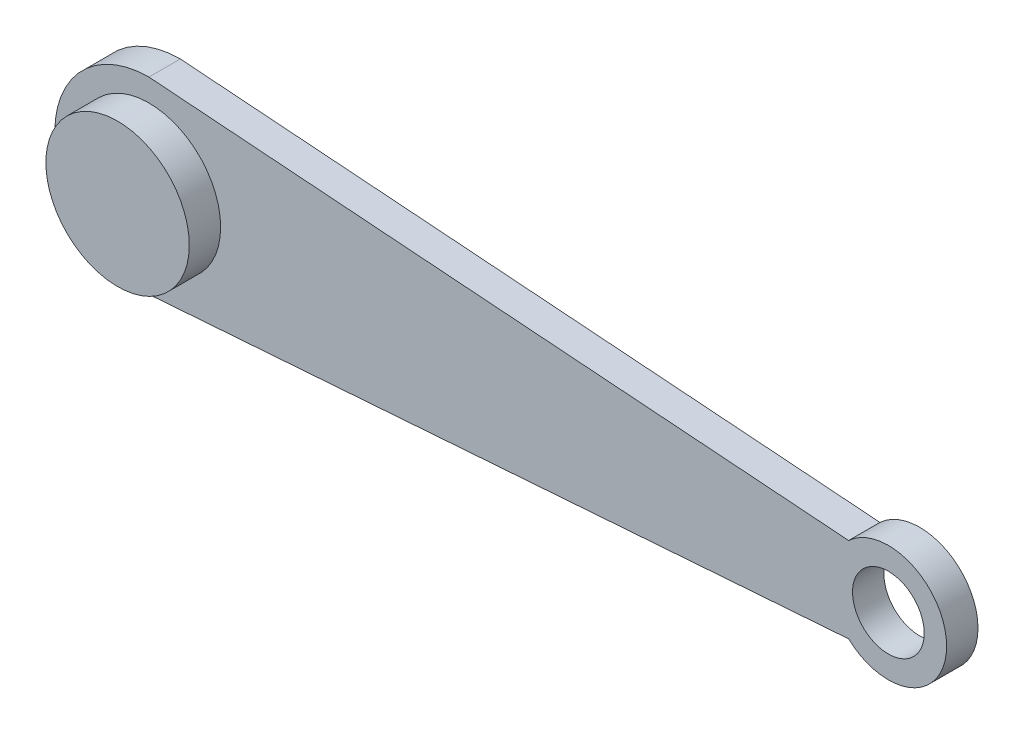
SolidWorks part; units mm, degrees
ref_plane "Front Plane" through (0, 0, 0) normal (0, 0, 1) x (1, 0, 0)
ref_plane "Top Plane" through (0, 0, 0) normal (0, 1, 0) x (1, 0, 0)
ref_plane "Right Plane" through (0, 0, 0) normal (1, 0, 0) x (0, 0, -1)
sketch "Sketch6" plane through (0, 0, 0) normal (0, 0, 1) x (1, 0, 0)
  line L0 (0, -21) -> (156.1259, -9.5)
  line L2 (0, 21) -> (156.1259, 9.5)
  line L3 (-58.5211, 0) -> (213.089, 0) construction
  circle A1 centre (165, 0) radius 8
  circle A2 centre (165, 0) radius 13
  circle A3 centre (0, 0) radius 16
  circle A4 centre (0, 0) radius 21
  dimension "D1" = 16
  dimension "D2" = 5
  dimension "D3" = 165
  dimension "D4" = 32
  dimension "D5" = 5
  dimension "D6" = 19
extrude "Boss-Extrude2" add sketch "Sketch6" along normal blind 7 contours A4 L3 A2 L2 | A4 L3 A3 L2 | L3 A4 L0 A3 | L3 A3 | A3 L3 | L3 A4 L0 A2 | L3 A2 A1 | L3 A1 | A1 L3 | A2 L3 A1 region at (-14.5172, -14.5172, 0) region at (77.3222, -7.8858, 0) region at (-14.5172, 14.5172, 0) region at (153.3426, -5.0628, 0) region at (77.3222, 7.8858, 0) region at (0, 6.7906, 0) region at (0, -6.7906, 0) region at (175.5, 0.2907, 0) region at (165, -3.3953, 0) region at (165, 3.3953, 0)
extrude "Boss-Extrude3" add sketch "Sketch6<10>" along normal blind 14 contours A3
sketch "Sketch6<10>" plane through (0, 0, 0) normal (0, 0, 1) x (1, 0, 0) same geometry as "Sketch6"
extrude "Cut-Extrude1" cut sketch "Sketch6<11>" along normal through all contours A1 L3 | L3 A1 region at (165, -3.3953, 0) region at (165, 3.3953, 0)
sketch "Sketch6<11>" plane through (0, 0, 0) normal (0, 0, 1) x (1, 0, 0) same geometry as "Sketch6"
